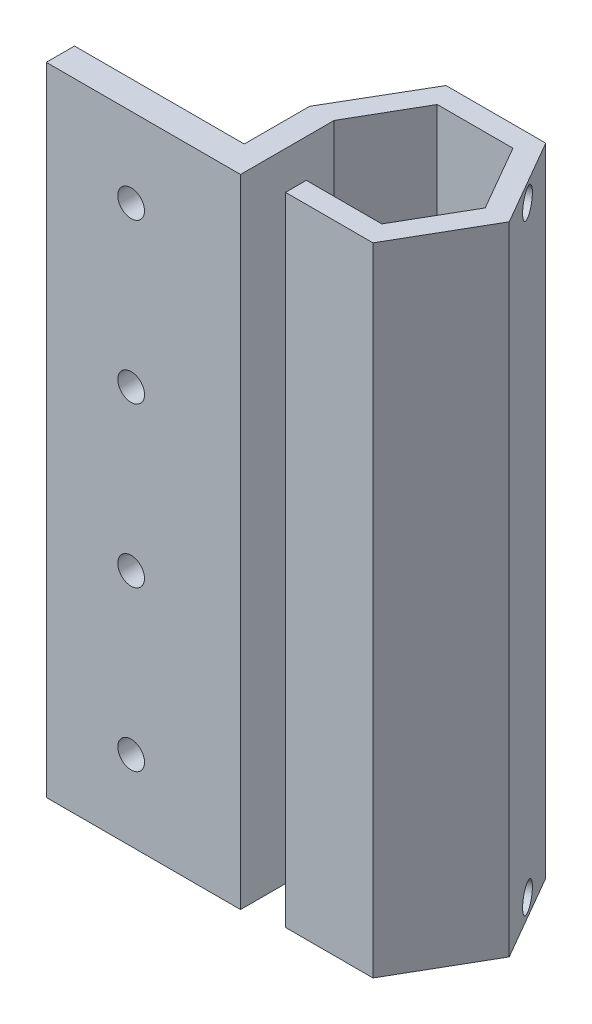
SolidWorks part; units mm, degrees
ref_plane "Front Plane" through (0, 0, 0) normal (0, 0, 1) x (1, 0, 0)
ref_plane "Top Plane" through (0, 0, 0) normal (0, 1, 0) x (1, 0, 0)
ref_plane "Right Plane" through (0, 0, 0) normal (1, 0, 0) x (0, 0, -1)
sketch "Sketch4" plane through (0, 0, 0) normal (0, 1, 0) x (1, 0, 0)
  line L1 (8.8623, 15.35) -> (-8.8623, 15.35) construction
  line L2 (-8.8623, 15.35) -> (-17.7247, 0) construction
  line L3 (-17.7247, 0) -> (-8.8623, -15.35) construction
  line L4 (-8.8623, -15.35) -> (8.8623, -15.35) construction
  line L5 (8.8623, -15.35) -> (17.7247, 0) construction
  line L6 (17.7247, 0) -> (8.8623, 15.35) construction
  line L30 (-17.8113, 0.05) -> (-17.8113, -22)
  line L33 (-23.5848, 0.05) -> (-23.5848, -15.35)
  line L36 (-8.8623, -20.35) -> (11.7491, -20.35)
  line L39 (-23.5848, -15.35) -> (-63.5848, -15.35)
  line L40 (-63.5848, -22) -> (-63.5848, -15.35)
  line L41 (-63.5848, -22) -> (-17.8113, -22)
  line L42 (-8.8623, -15.45) -> (8.9201, -15.45)
  line L43 (8.9201, -15.45) -> (17.8401, 0)
  line L44 (17.8401, 0) -> (8.9201, 15.45)
  line L45 (8.9201, 15.45) -> (-8.9201, 15.45)
  line L46 (-8.9201, 15.45) -> (-17.8113, 0.05)
  line L47 (11.7491, -20.35) -> (23.4982, 0)
  line L48 (23.4982, 0) -> (11.7491, 20.35)
  line L49 (11.7491, 20.35) -> (-11.7491, 20.35)
  line L50 (-11.7491, 20.35) -> (-23.5848, 0.05)
  line L51 (-11.7491, 20.35) -> (-22.0548, 2.5) construction
  line L52 (-8.8623, -20.35) -> (-8.8623, -15.45)
  circle A0 centre (0, 0) radius 15.35 construction
  dimension "D2" = 0.1
  dimension "D1" = 30.7
  dimension "D3" = 5
  dimension "D4" = 6.65
  dimension "D5" = 22.05
  dimension "D6" = 40
  dimension "D7" = 15.4
  dimension "D8" = 20.3
  dimension "D9" = 179.756
extrude "Boss-Extrude3" add sketch "Sketch4" against normal blind 150 contours L39 L40 L41 L30 L46 L45 L44 L43 L42 L52 L36 L47 L48 L49 L50 L33
sketch "Sketch5" plane through (0, 0, 15.35) normal (0, 0, -1) x (-1, 0, 0)
  line L2 (23.5848, -150) -> (63.5848, -150) construction
  line L3 (43.5848, -75) -> (63.5848, -75) construction
  line L4 (63.5848, -150) -> (63.5848, 0) construction
  line L8 (43.5848, -112.5) -> (63.5848, -112.5) construction
  line L9 (43.5848, -75) -> (43.5848, -112.5) construction
  line L13 (43.5848, -150) -> (43.5848, -112.5) construction
  line L14 (43.5848, -112.5) -> (43.5848, -150) construction
  line L17 (43.5848, -37.5) -> (63.5848, -37.5) construction
  line L18 (43.5848, -37.5) -> (43.5848, -75) construction
  line L19 (43.5848, 0) -> (43.5848, -37.5) construction
  line L20 (23.5848, 0) -> (63.5848, 0) construction
  circle A3 centre (43.5848, -131.25) radius 3.15
  circle A4 centre (43.5848, -93.75) radius 3.15
  circle A5 centre (43.5848, -56.25) radius 3.15
  circle A6 centre (43.5848, -18.75) radius 3.15
  dimension "D1" = 6.3
  dimension "D2" = 6.3
  dimension "D3" = 6.3
  dimension "D4" = 6.3
extrude "Cut-Extrude1" cut sketch "Sketch5" against normal blind 10 contours A3 | A4 | A5 | A6
sketch "Sketch6" plane through (17.6236, 0, -10.175) normal (0.866, 0, -0.5) x (-0.5, 0, -0.866)
  line L0 (0, 0) -> (0, -150) construction
  line L2 (-11.7491, -150) -> (11.7491, -150) construction
  line L4 (0, 0) -> (0, -1) construction
  line L5 (0, -7.3) -> (0, -25.7) construction
  line L7 (0, -150) -> (0, -149) construction
  circle A2 centre (0, -4.15) radius 3.15
  circle A3 centre (0, -145.85) radius 3.15
  dimension "D1" = 1
  dimension "D2" = 6.3
  dimension "D4" = 6.3
  dimension "D3" = 1
  dimension "D5" = 18.4
extrude "Cut-Extrude3" cut sketch "Sketch6" against normal blind 10 contours A3 | A2
sketch "Sketch7" plane through (17.6236, 0, -10.175) normal (0.866, 0, -0.5) x (-0.5, 0, -0.866)
  line L0 (0, -7.3) -> (0, -25.7) construction
  line L1 (-11.7491, -25.7) -> (11.7491, -25.7)
  line L2 (-11.7491, -150) -> (-11.7491, 0) construction
  line L4 (11.7491, -25.7) -> (11.7491, -27.2994)
  line L5 (11.7491, -27.2994) -> (-11.7491, -27.2994)
  line L6 (-11.7491, -27.2994) -> (-11.7491, -25.7)
  line L7 (0, -142.7) -> (0, -124.3) construction
  line L8 (-11.7491, -124.3) -> (11.7491, -124.3)
  line L9 (11.7491, -124.3) -> (11.7491, -122.7)
  line L10 (11.7491, -122.7) -> (-11.7491, -122.7)
  line L11 (-11.7491, -122.7) -> (-11.7491, -124.3)
  line L12 (11.7491, -150) -> (11.7491, 0) construction
  line L13 (11.7491, -150) -> (11.7491, 0) construction
  circle A0 centre (0, -4.15) radius 3.15 construction
  circle A1 centre (0, -145.85) radius 3.15 construction
  point P9 (11.7491, -124.3)
  point P10 (11.7491, -120.5327)
  point P20 (0, 0)
  point P25 (0, 0)
  point P26 (11.7491, -27.2994)
  point P27 (11.7491, -25.7)
  dimension "D1" = 18.4
  dimension "D2" = 18.4
  dimension "D3" = 1.6
  dimension "D4" = 1.5994
extrude "Boss-Extrude4" add sketch "Sketch7" against normal blind 10
